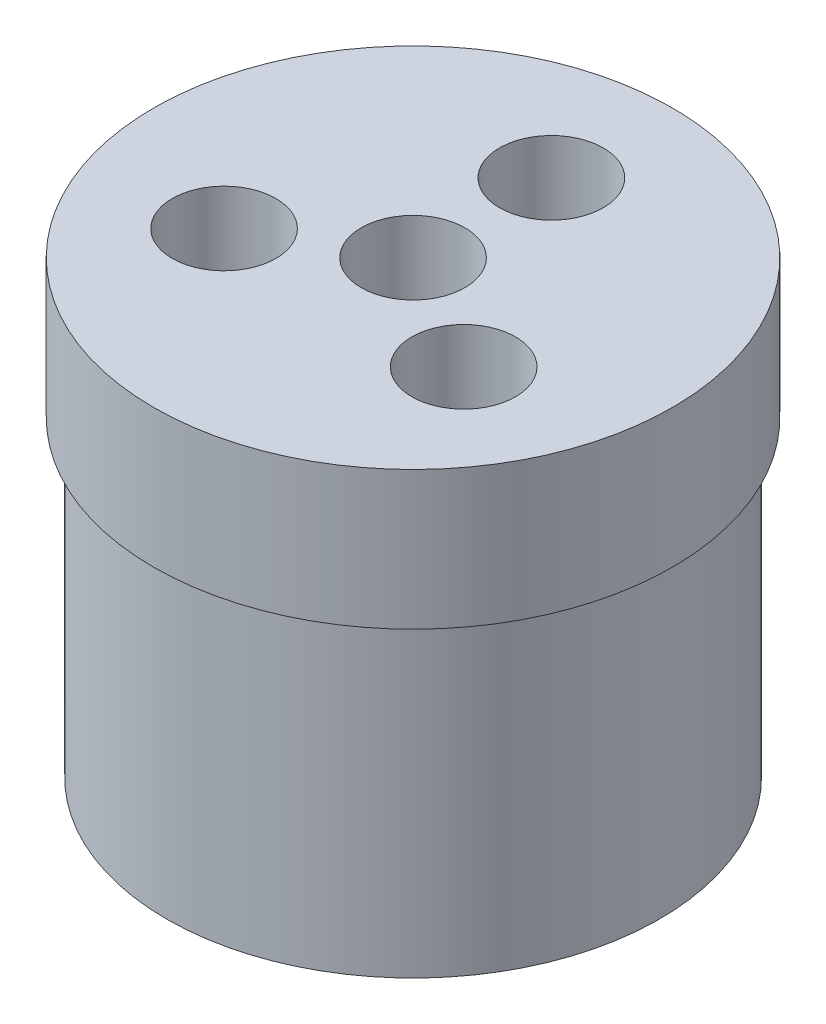
SolidWorks part; units mm, degrees
ref_plane "정면" through (0, 0, 0) normal (0, 0, 1) x (1, 0, 0)
ref_plane "윗면" through (0, 0, 0) normal (0, 1, 0) x (1, 0, 0)
ref_plane "우측면" through (0, 0, 0) normal (1, 0, 0) x (0, 0, -1)
sketch "스케치1" plane through (0, 0, 0) normal (0, 1, 0) x (1, 0, 0)
  circle A0 centre (0, 0) radius 15
  circle A1 centre (0, 0) radius 14.25
  dimension "D1" = 30
  dimension "D2" = 28.5
extrude "보스-돌출1" add sketch "스케치1" along normal blind 8 contours A0
extrude "보스-돌출2" add sketch "스케치1<3>" against normal blind 18 contours A1
sketch "스케치1<3>" plane through (0, 0, 0) normal (0, 1, 0) x (1, 0, 0) same geometry as "스케치1"
sketch "스케치2" plane through (0, 8, 0) normal (0, 1, 0) x (1, 0, 0)
  circle A0 centre (0, 0) radius 8 construction
  circle A1 centre (0, 8) radius 3
  circle A2 centre (0, 0) radius 3
  circle A3 centre (6.9282, -4) radius 3
  circle A4 centre (-6.9282, -4) radius 3
  point P12 (0, 0)
  dimension "D1" = 16
  dimension "D2" = 6
  dimension "D3" = 6
  dimension "D4" = 3
extrude "컷-돌출1" cut sketch "스케치2" against normal through all contours A2 | A1 | A3 | A4 region at (0, 8, -8) region at (0, 8, 0) region at (6.9282, 8, 4)
